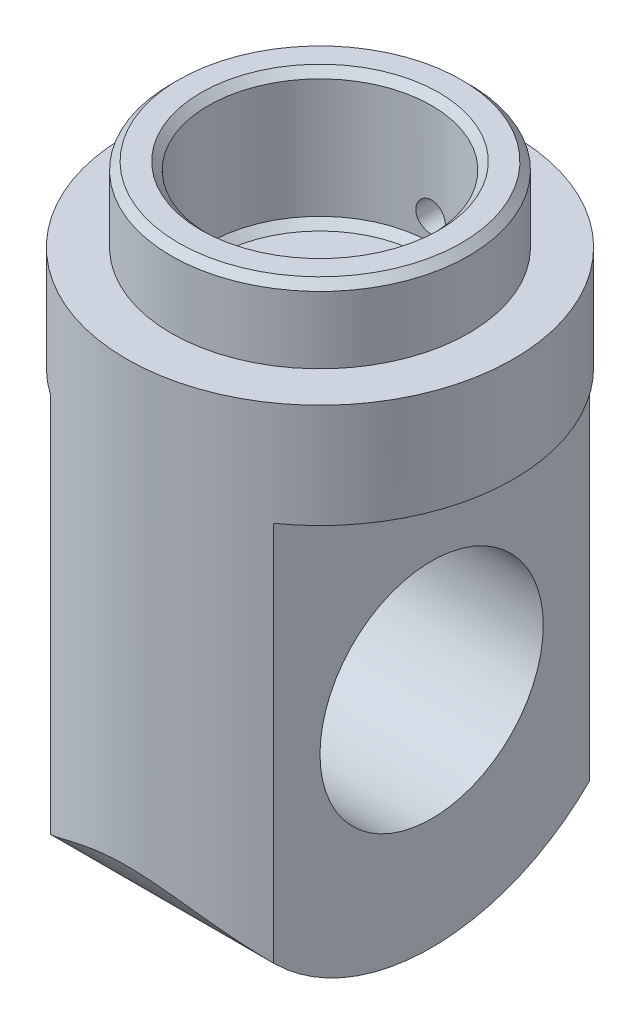
SolidWorks part; units mm, degrees
ref_plane "Front Plane" through (0, 0, 0) normal (0, 0, 1) x (1, 0, 0)
ref_plane "Top Plane" through (0, 0, 0) normal (0, 1, 0) x (1, 0, 0)
ref_plane "Right Plane" through (0, 0, 0) normal (1, 0, 0) x (0, 0, -1)
sketch "Sketch1" plane through (0, 0, 0) normal (0, 1, 0) x (1, 0, 0)
  circle A0 centre (0, 0) radius 13
  dimension "D1" = 26
extrude "Boss-Extrude1" add sketch "Sketch1" along normal blind 7
sketch "Sketch2" plane through (0, 7, 0) normal (0, 1, 0) x (1, 0, 0)
  circle A0 centre (0, 0) radius 10
  dimension "D1" = 20
extrude "Boss-Extrude2" add sketch "Sketch2" along normal blind 5
sketch "Sketch3" plane through (0, 12, 0) normal (0, 1, 0) x (1, 0, 0)
  circle A0 centre (0, 0) radius 7.5
  dimension "D1" = 15
extrude "Cut-Extrude1" cut sketch "Sketch3" against normal blind 9
chamfer "Chamfer1" distance 0.5 angle 45 3 edges at (0, 12, 10) (0, 3, 7.5) (0, 12, 7.5)
sketch "Sketch4" plane through (0, 0, 0) normal (0, 0, 1) x (1, 0, 0)
  circle A0 centre (0, 5) radius 1
  point P2 (0, 0)
  dimension "D1" = 2
  dimension "D2" = 5
extrude "Cut-Extrude2" cut sketch "Sketch4" against normal through all
sketch "Sketch5" plane through (0, 0, 0) normal (0, -1, 0) x (1, 0, 0)
  line L1 (-7.5, -13) -> (7.5, -13)
  line L2 (-7.5, -13) -> (-7.5, 13)
  line L3 (-7.5, 13) -> (7.5, 13)
  line L4 (7.5, -13) -> (7.5, 13)
  line L5 (-7.5, -13) -> (7.5, 13) construction
  line L6 (-7.5, 13) -> (7.5, -13) construction
  circle A0 centre (0, 0) radius 13 construction
  point P0 (0, 0)
  dimension "D1" = 15
extrude "Boss-Extrude3" add sketch "Sketch5" along normal blind 30
sketch "Sketch7" plane through (0, 0, 0) normal (0, -1, 0) x (1, 0, 0)
  circle A0 centre (0, 0) radius 13
  arc A1 (7.5, -10.6184) -> (7.5, 10.6184) centre (0, 0) ccw construction
  circle A2 centre (0, 0) radius 20
  dimension "D1" = 40
extrude "Cut-Extrude3" cut sketch "Sketch7" along normal through all
sketch "Sketch8" plane through (-7.5, 0, 0) normal (-1, 0, 0) x (0, 0, 1)
  circle A0 centre (0, -15) radius 7.5
  point P2 (-0.3335, -11.335)
  point P4 (0, 0)
  dimension "D1" = 15
  dimension "D2" = 15
extrude "Cut-Extrude4" cut sketch "Sketch8" against normal up to surface (15 mm away) up to face at (7.5, -15, 0)
sketch "Sketch9" plane through (7.5, 0, 0) normal (1, 0, 0) x (0, 0, -1)
  line L0 (-13, 7) -> (-13, -30) construction
  line L1 (13, -30) -> (13, 4) construction
  line L2 (-13, -22.4833) -> (-14, -22.4833)
  line L3 (-14, -22.4833) -> (-14, -31)
  line L4 (-14, -31) -> (14, -31)
  line L5 (14, -31) -> (14, -22.4833)
  line L6 (14, -22.4833) -> (13, -22.4833)
  line L7 (10.6184, -30) -> (-10.6184, -30) construction
  arc A0 (-13, -22.4833) -> (13, -22.4833) centre (0, -15) ccw
  circle A1 centre (0, -15) radius 7.5 construction
  dimension "D1" = 15
  dimension "D2" = 1
  dimension "D3" = 1
  dimension "D4" = 1
extrude "Cut-Extrude5" cut sketch "Sketch9" against normal up to surface (15 mm away) up to face at (-7.5, -15, 7.5)
